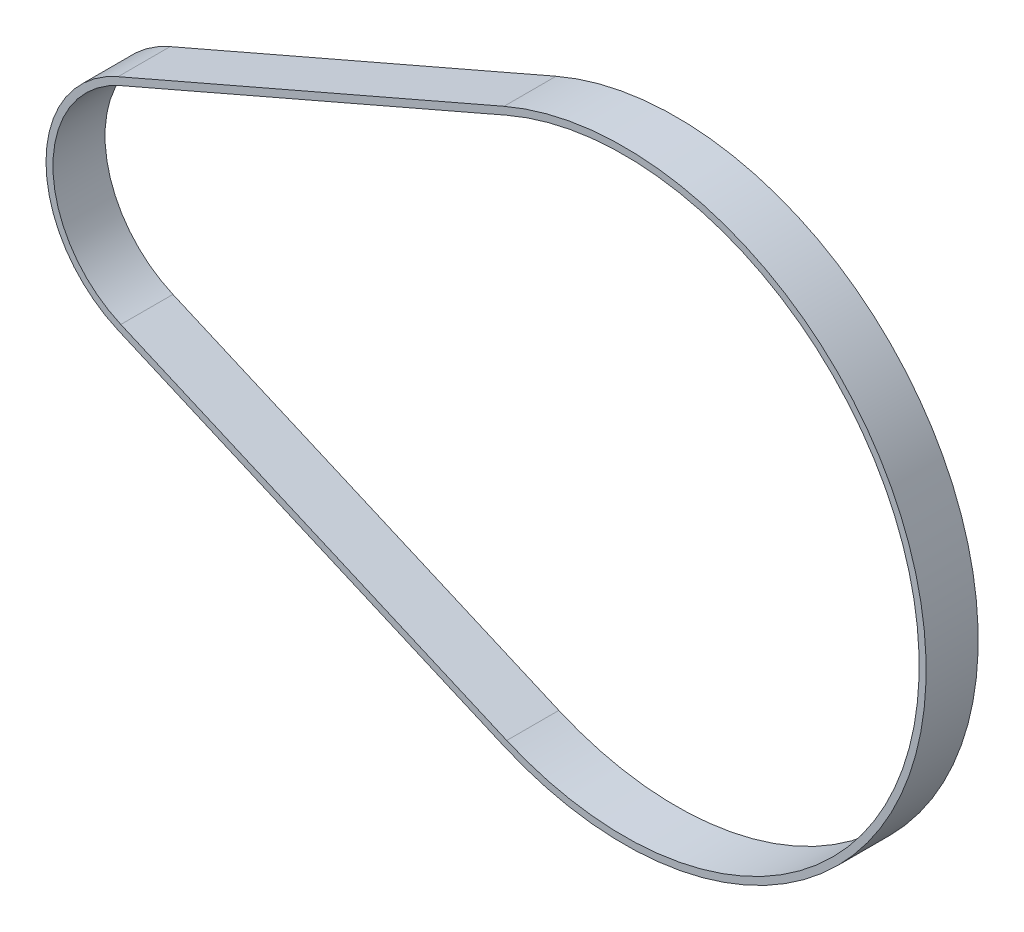
SolidWorks part; units mm, degrees
ref_plane "前视基准面" through (0, 0, 0) normal (0, 0, 1) x (1, 0, 0)
ref_plane "上视基准面" through (0, 0, 0) normal (0, 1, 0) x (1, 0, 0)
ref_plane "右视基准面" through (0, 0, 0) normal (1, 0, 0) x (0, 0, -1)
other "Configuration Table"
ref_plane "基准面1" through (0, 0, 0) normal (0, 0, 1) x (1, 0, 0)
sketch "草图1" plane through (0, 0, 0) normal (0, 0, 1) x (1, 0, 0)
  line L0 (-5.484, -12.6505) -> (38.9802, -31.9257)
  line L1 (38.9802, 31.9257) -> (-5.484, 12.6505)
  line L2 (-5.1658, -11.9165) -> (39.2984, -31.1917)
  line L3 (39.2984, 31.1917) -> (-5.1658, 11.9165)
  arc A0 (-5.484, 12.6505) -> (-5.484, -12.6505) centre (0, 0) ccw
  arc A1 (38.9802, -31.9257) -> (38.9802, 31.9257) centre (52.82, 0) ccw
  arc A2 (-5.1658, 11.9165) -> (-5.1658, -11.9165) centre (0, 0) ccw
  arc A3 (39.2984, -31.1917) -> (39.2984, 31.1917) centre (52.82, 0) ccw
extrude "凸台-拉伸1" add sketch "草图1" against normal blind 3 and the other way blind 3
